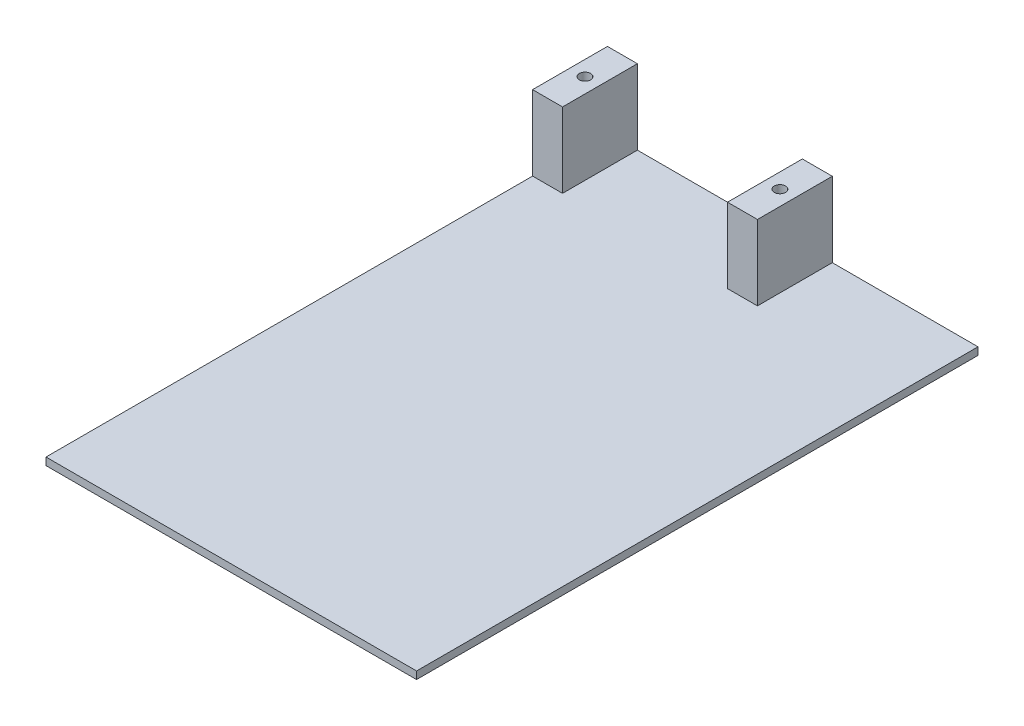
SolidWorks part; units mm, degrees
ref_plane "Front Plane" through (0, 0, 0) normal (0, 0, 1) x (1, 0, 0)
ref_plane "Top Plane" through (0, 0, 0) normal (0, 1, 0) x (1, 0, 0)
ref_plane "Right Plane" through (0, 0, 0) normal (1, 0, 0) x (0, 0, -1)
sketch "Sketch1" plane through (0, 0, 0) normal (0, 1, 0) x (1, 0, 0)
  line L1 (0, 0) -> (99, 0)
  line L2 (0, 0) -> (0, 150)
  line L3 (0, 150) -> (99, 150)
  line L4 (99, 0) -> (99, 150)
  dimension "D1" = 99
  dimension "D2" = 150
extrude "Boss-Extrude1" add sketch "Sketch1" along normal blind 2
sketch "Sketch2" plane through (0, 2, 0) normal (0, 1, 0) x (1, 0, 0)
  line L0 (0, 150) -> (8, 150)
  line L1 (99, 150) -> (0, 150) construction
  line L2 (8, 150) -> (8, 130)
  line L3 (8, 130) -> (0, 130)
  line L4 (0, 150) -> (0, 0) construction
  line L5 (0, 130) -> (0, 150)
  line L6 (0, 150) -> (60.075, 150) construction
  line L8 (60.075, 150) -> (52.075, 150)
  line L9 (60.075, 150) -> (60.075, 130)
  line L10 (60.075, 130) -> (52.075, 130)
  line L11 (52.075, 150) -> (52.075, 130)
  dimension "D1" = 8
  dimension "D2" = 20
  dimension "D3" = 60.075
  dimension "D4" = 8
  dimension "D5" = 20
extrude "Boss-Extrude2" add sketch "Sketch2" along normal blind 20 contours L5 L0 L2 L3 | L9 L8 L11 L10
sketch "Sketch3" plane through (0, 22, 0) normal (0, 1, 0) x (1, 0, 0)
  line L4 (0, 140) -> (8, 140) construction
  line L5 (0, 130) -> (0, 150) construction
  line L6 (8, 150) -> (8, 130) construction
  line L9 (52.075, 140) -> (60.075, 140) construction
  line L10 (52.075, 150) -> (52.075, 130) construction
  line L11 (60.075, 150) -> (60.075, 130) construction
  circle A0 centre (4, 140) radius 1.5
  circle A2 centre (56.075, 140) radius 1.5
  dimension "D1" = 3
  dimension "D2" = 3
  dimension "D3" = 4
  dimension "D4" = 4
extrude "Cut-Extrude2" cut sketch "Sketch3" against normal blind 15 contours A2 | A0 region at (56.075, 22, -140)
